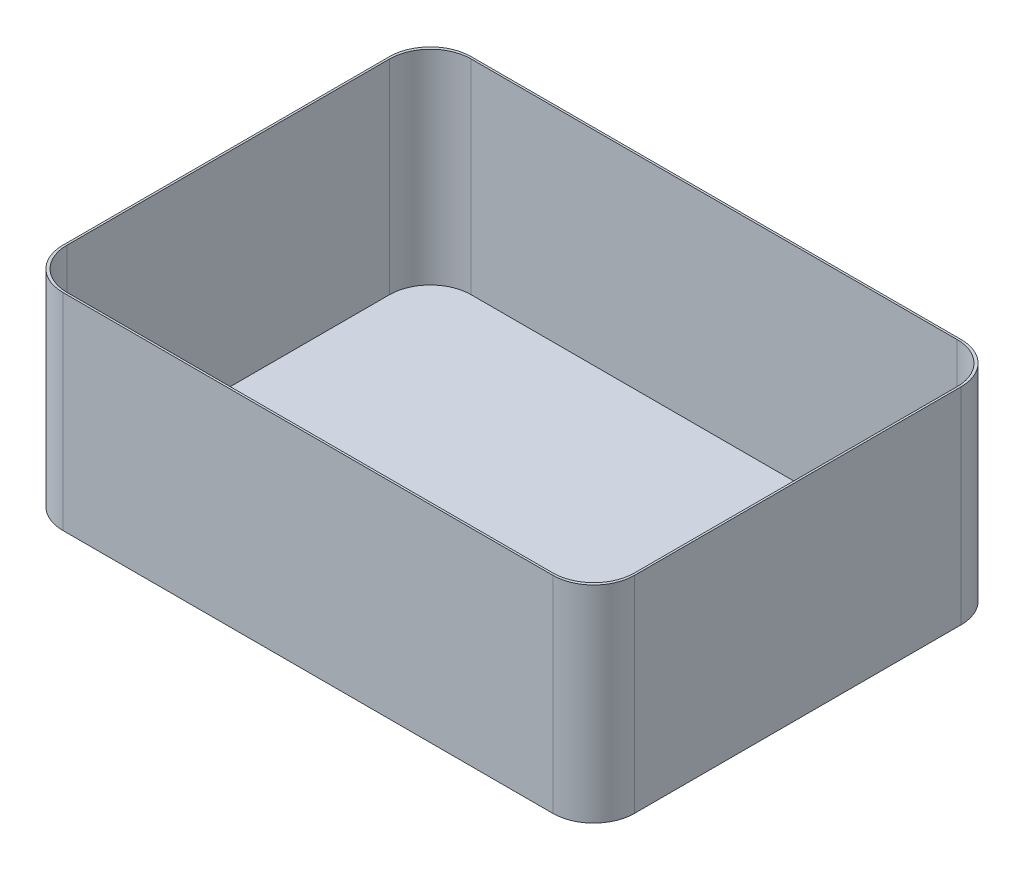
SolidWorks part; units mm, degrees
ref_plane "Front Plane" through (0, 0, 0) normal (0, 0, 1) x (1, 0, 0)
ref_plane "Top Plane" through (0, 0, 0) normal (0, 1, 0) x (1, 0, 0)
ref_plane "Right Plane" through (0, 0, 0) normal (1, 0, 0) x (0, 0, -1)
sketch "Sketch1" plane through (0, 0, 0) normal (0, 1, 0) x (1, 0, 0)
  line L1 (-355.6, -254) -> (355.6, -254)
  line L2 (-355.6, -254) -> (-355.6, 254)
  line L3 (-355.6, 254) -> (355.6, 254)
  line L4 (355.6, -254) -> (355.6, 254)
  line L5 (-355.6, -254) -> (355.6, 254) construction
  line L6 (-355.6, 254) -> (355.6, -254) construction
  line L7 (-353.06, -251.46) -> (353.06, -251.46)
  line L8 (-353.06, -251.46) -> (-353.06, 251.46)
  line L9 (-353.06, 251.46) -> (353.06, 251.46)
  line L10 (353.06, -251.46) -> (353.06, 251.46)
  line L11 (-353.06, -251.46) -> (353.06, 251.46) construction
  line L12 (-353.06, 251.46) -> (353.06, -251.46) construction
  point P0 (0, 0)
  point P6 (0, 0)
  dimension "D1" = 508
  dimension "D2" = 711.2
  dimension "D3" = 2.54
  dimension "D4" = 2.54
extrude "Boss-Extrude1" add sketch "Sketch1" along normal blind 254
sketch "Sketch2" plane through (0, 0, 0) normal (0, -1, 0) x (1, 0, 0)
  line L1 (355.6, 254) -> (-355.6, 254)
  line L2 (355.6, 254) -> (355.6, -254)
  line L3 (355.6, -254) -> (-355.6, -254)
  line L4 (-355.6, 254) -> (-355.6, -254)
  line L5 (355.6, 254) -> (-355.6, -254) construction
  line L6 (355.6, -254) -> (-355.6, 254) construction
  point P0 (0, 0)
extrude "Boss-Extrude2" add sketch "Sketch2" along normal blind 2.54
fillet "Fillet1" radius 50.8 8 edges at (353.06, 127, 251.46) (-353.06, 127, 251.46) (-353.06, 127, -251.46) (353.06, 127, -251.46) (355.6, 125.73, -254) (355.6, 125.73, 254) (-355.6, 125.73, 254) (-355.6, 125.73, -254)
